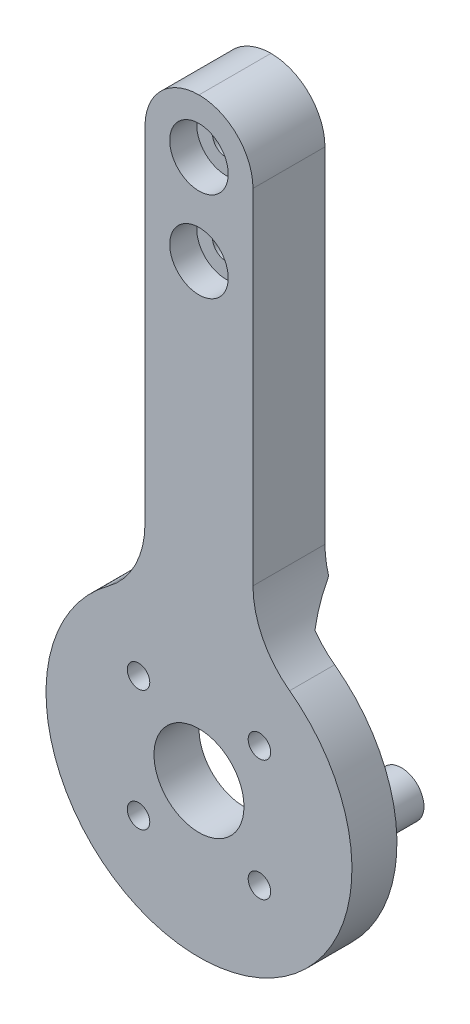
SolidWorks part; units mm, degrees
ref_plane "Piano frontale" through (0, 0, 0) normal (0, 0, 1) x (1, 0, 0)
ref_plane "Piano superiore" through (0, 0, 0) normal (0, 1, 0) x (1, 0, 0)
ref_plane "Piano destro" through (0, 0, 0) normal (1, 0, 0) x (0, 0, -1)
sketch "Schizzo1" plane through (0, 0, 0) normal (0, 0, 1) x (1, 0, 0)
  line L0 (0, 0) -> (0, -60) construction
  line L1 (-6, -44.094) -> (-6, 6)
  line L2 (-6, 6) -> (6, 6)
  line L3 (6, 6) -> (6, -44.094)
  line L4 (6.7175, -53.2825) -> (6.7175, -66.7175) construction
  circle A0 centre (0, 0) radius 1.5
  circle A1 centre (0, -10) radius 1.5
  circle A2 centre (6.7175, -53.2825) radius 1.25
  circle A3 centre (6.7175, -66.7175) radius 1.25
  circle A4 centre (-6.7175, -66.7175) radius 1.25
  circle A5 centre (-6.7175, -53.2825) radius 1.25
  arc A6 (-6, -44.094) -> (6, -44.094) centre (0, -60) ccw
  circle A7 centre (0, -60) radius 5
  point P17 (0, -60)
  dimension "D1" = 3
  dimension "D4" = 2.5
  dimension "D8" = 34
  dimension "D11" = 10
  dimension "D3" = 10
  dimension "D6" = 19
  dimension "D7" = 60
  dimension "D9" = 12
  dimension "D10" = 6
  dimension "D2" = 2
  dimension "D5" = 4
extrude "Estrusione-Estrusione1" add sketch "Schizzo1" along normal blind 5
sketch "Schizzo2" plane through (0, 0, 0) normal (0, 0, -1) x (-1, 0, 0)
  line L0 (-6, -44.094) -> (6, -44.094)
  line L3 (6, -44.094) -> (6, 6)
  line L4 (6, 6) -> (-6, 6)
  line L5 (-6, 6) -> (-6, -44.094)
  line L6 (6, -44.094) -> (6, 6)
  line L7 (6, 6) -> (-6, 6)
  line L8 (-6, 6) -> (-6, -44.094)
  arc A1 (-6, -44.094) -> (6, -44.094) centre (0, -60) ccw
  arc A2 (-6, -44.094) -> (6, -44.094) centre (0, -60) ccw
  line M6 (6, -44.094) -> (6, 6)
  line M7 (6, 6) -> (-6, 6)
  line M8 (-6, 6) -> (-6, -44.094)
  circle M9 centre (0, 0) radius 1.5
  circle M10 centre (0, -10) radius 1.5
  dimension "D1" = 0
extrude "Estrusione-Estrusione2" add sketch "Schizzo2" along normal blind 3 contours L0 M8 M6 M7 M10 M9 region at (0, -19.3853, 0)
chamfer "Smusso1" distance 3 angle 45 1 edges at (0, -44.094, -3)
chamfer "Smusso2" distance 1.5 angle 45 4 edges at (7.9675, -66.7175, 0) (-5.4675, -66.7175, 0) (-5.4675, -53.2825, 0) (7.9675, -53.2825, 0)
fillet "Raccordo1" radius 10 2 edges at (-6, -44.094, 2.5) (6, -44.094, 2.5)
fillet "Raccordo2" radius 6 2 edges at (-6, 6, 1) (6, 6, 1)
sketch "Schizzo3" plane through (0, 0, 5) normal (0, 0, 1) x (1, 0, 0)
  circle A0 centre (0, 0) radius 3.25
  circle A1 centre (0, -10) radius 3.25
  dimension "D1" = 6.5
extrude "Taglio-Estrusione1" cut sketch "Schizzo3" against normal blind 3
sketch "Schizzo5" plane through (0, 0, 0) normal (0, 0, -1) x (-1, 0, 0)
  line L0 (0, -60) -> (0, 0) construction
  line L1 (-6, -60) -> (0, -60) construction
  circle A0 centre (-6, -60) radius 0.85
  circle A1 centre (-6, -60) radius 2
  circle A2 centre (0, -60) radius 5 construction
  circle A3 centre (0, -60) radius 5 construction
  circle A4 centre (6, -60) radius 2
  circle A5 centre (6, -60) radius 0.85
  dimension "D1" = 1.7
  dimension "D2" = 4
  dimension "D3" = 12
extrude "Estrusione-Estrusione3" [suppressed] add sketch "Schizzo5" along normal blind 5
chamfer "Smusso4" [suppressed] distance 1.5 angle 45
sketch "Schizzo6" plane through (0, 0, 0) normal (0, 0, -1) x (-1, 0, 0)
  line L0 (0, -60) -> (0, -47.5) construction
  circle A0 centre (0, -60) radius 5 construction
  circle A1 centre (0, -60) radius 5 construction
  circle A2 centre (0, -47.5) radius 1.15
  circle A3 centre (0, -47.5) radius 2.5
  circle A4 centre (12.5, -60) radius 2.5
  circle A5 centre (12.5, -60) radius 1.15
  circle A6 centre (0, -72.5) radius 2.5
  circle A7 centre (0, -72.5) radius 1.15
  circle A8 centre (-12.5, -60) radius 2.5
  circle A9 centre (-12.5, -60) radius 1.15
  point P19 (0, -60)
  dimension "D1" = 2.3
  dimension "D2" = 5
  dimension "D4" = 25
  dimension "D3" = 4
extrude "Estrusione-Estrusione4" add sketch "Schizzo6" along normal blind 5
chamfer "Smusso5" distance 1.5 angle 45 4 edges at (-10, -60, 0) (2.5, -72.5, 0) (15, -60, 0) (2.5, -47.5, 0)
